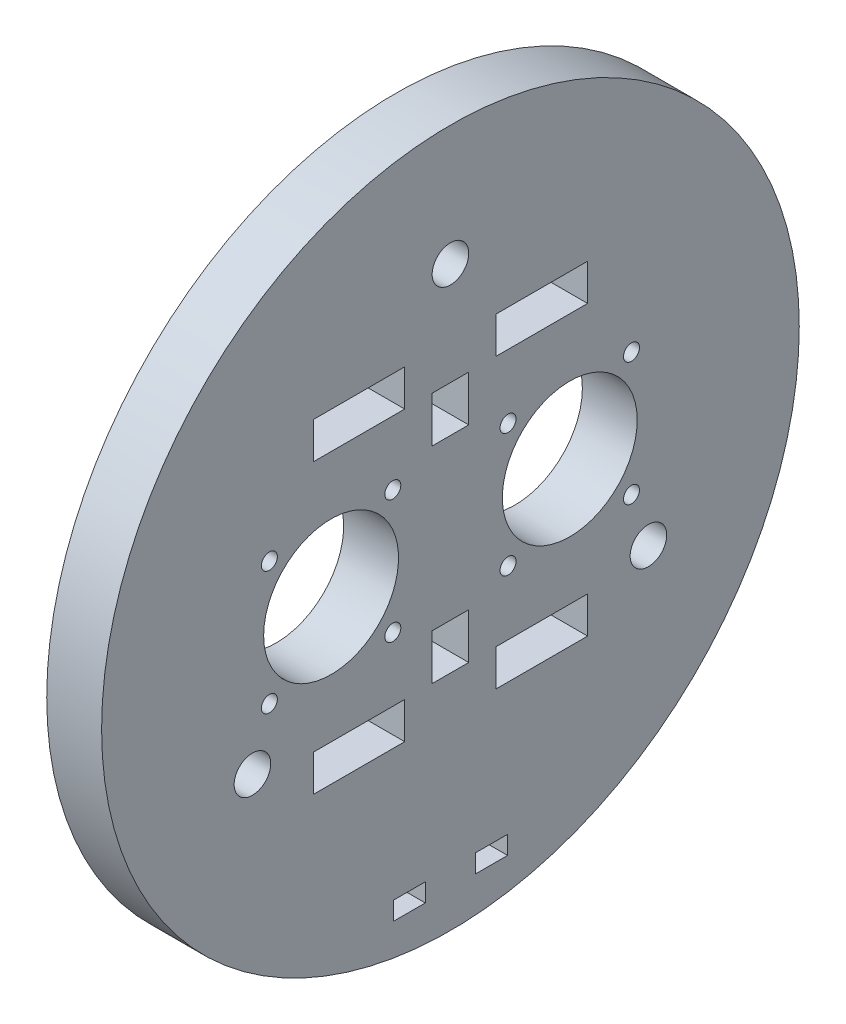
SolidWorks part; units mm, degrees
ref_plane "Front Plane" through (0, 0, 0) normal (0, 0, 1) x (1, 0, 0)
ref_plane "Top Plane" through (0, 0, 0) normal (0, 1, 0) x (1, 0, 0)
ref_plane "Right Plane" through (0, 0, 0) normal (1, 0, 0) x (0, 0, -1)
sketch "Sketch1" plane through (0, 0, 0) normal (1, 0, 0) x (0, 0, -1)
  line L0 (0, -76.29) -> (0, 76.29) construction
  line L1 (-76.29, 0) -> (76.29, 0) construction
  line L2 (26.1, 0) -> (39.5969, 13.4969) construction
  circle A0 centre (0, 0) radius 76.29
  circle A1 centre (0, 50) radius 4
  circle A2 centre (43.3013, -25) radius 4
  circle A3 centre (-43.3013, -25) radius 4
  circle A4 centre (26.1, 0) radius 14.75
  circle A5 centre (-26.1, 0) radius 14.75
  circle A6 centre (39.5969, 13.4969) radius 1.75
  circle A7 centre (39.5969, -13.4969) radius 1.75
  circle A8 centre (12.6031, -13.4969) radius 1.75
  circle A9 centre (12.6031, 13.4969) radius 1.75
  circle A10 centre (-39.5969, -13.4969) radius 1.75
  circle A11 centre (-12.6031, -13.4969) radius 1.75
  circle A12 centre (-12.6031, 13.4969) radius 1.75
  circle A13 centre (-39.5969, 13.4969) radius 1.75
  circle A14 centre (26.1, 0) radius 22.1 construction
  circle A15 centre (-26.1, 0) radius 22.1 construction
  point P12 (0, 0)
  point P29 (26.1, 0)
  point P37 (-4, 0)
  point P40 (4, 0)
  dimension "D1" = 152.58
  dimension "D2" = 8
  dimension "D5" = 29.5
  dimension "D7" = 3.5
  dimension "D11" = 44.2
  dimension "D3" = 50
  dimension "D4" = 3
  dimension "D6" = 8
  dimension "D8" = 19.0875
  dimension "D10" = 45
  dimension "D9" = 4
extrude "Boss-Extrude1" add sketch "Sketch1" along normal blind 12
sketch "Sketch2" plane through (12, 0, 0) normal (1, 0, 0) x (0, 0, -1)
  line L0 (-97.5918, 0) -> (102.3086, 0) construction
  line L1 (0, 96.3466) -> (0, -103.9448) construction
  line L2 (10, -27.5) -> (10, -35.5)
  line L3 (-30, -27.5) -> (-10, -27.5)
  line L4 (-30, -27.5) -> (-30, -35.5)
  line L5 (-30, -35.5) -> (-10, -35.5)
  line L6 (-10, -27.5) -> (-10, -35.5)
  line L7 (30, -27.5) -> (10, -27.5)
  line L8 (30, -27.5) -> (30, -35.5)
  line L9 (30, -35.5) -> (10, -35.5)
  line L10 (-30, 27.5) -> (-30, 35.5)
  line L11 (-30, 35.5) -> (-10, 35.5)
  line L12 (-10, 27.5) -> (-10, 35.5)
  line L13 (-30, 27.5) -> (-10, 27.5)
  line L14 (10, 27.5) -> (10, 35.5)
  line L15 (30, 35.5) -> (10, 35.5)
  line L16 (30, 27.5) -> (10, 27.5)
  line L17 (30, 27.5) -> (30, 35.5)
  line L18 (-4, -17.5) -> (4, -17.5)
  line L19 (-4, 27.5) -> (4, 27.5)
  line L20 (-4, 27.5) -> (-4, 17.5)
  line L21 (-4, 17.5) -> (4, 17.5)
  line L22 (4, 27.5) -> (4, 17.5)
  line L23 (-4, -27.5) -> (-4, -17.5)
  line L24 (-4, -27.5) -> (4, -27.5)
  line L25 (4, -27.5) -> (4, -17.5)
  line L26 (27.8787, -35.5) -> (30, -33.3787) construction
  line L27 (-42.3534, -68.29) -> (39.6493, -68.29) construction
  line L28 (-5.5, -68.29) -> (-5.5, -64.29)
  line L29 (12.5, -68.29) -> (5.5, -68.29)
  line L30 (12.5, -68.29) -> (12.5, -64.29)
  line L31 (12.5, -64.29) -> (5.5, -64.29)
  line L32 (5.5, -68.29) -> (5.5, -64.29)
  line L33 (-12.5, -64.29) -> (-5.5, -64.29)
  line L34 (-12.5, -68.29) -> (-12.5, -64.29)
  line L35 (-12.5, -68.29) -> (-5.5, -68.29)
  circle A0 centre (30, -35.5) radius 2.1213 construction
  circle A1 centre (0, 0) radius 76.29 construction
  point P23 (0, 27.5)
  point P31 (30, -33.3787)
  point P32 (0, -76.29)
  point P33 (27.8787, -35.5)
  dimension "D1" = 27.5
  dimension "D2" = 8
  dimension "D3" = 20
  dimension "D4" = 20
  dimension "D5" = 8
  dimension "D6" = 10
  dimension "D7" = 8
  dimension "D8" = 4
  dimension "D9" = 7
  dimension "D10" = 25
extrude "Cut-Extrude1" cut sketch "Sketch2" against normal blind 8
